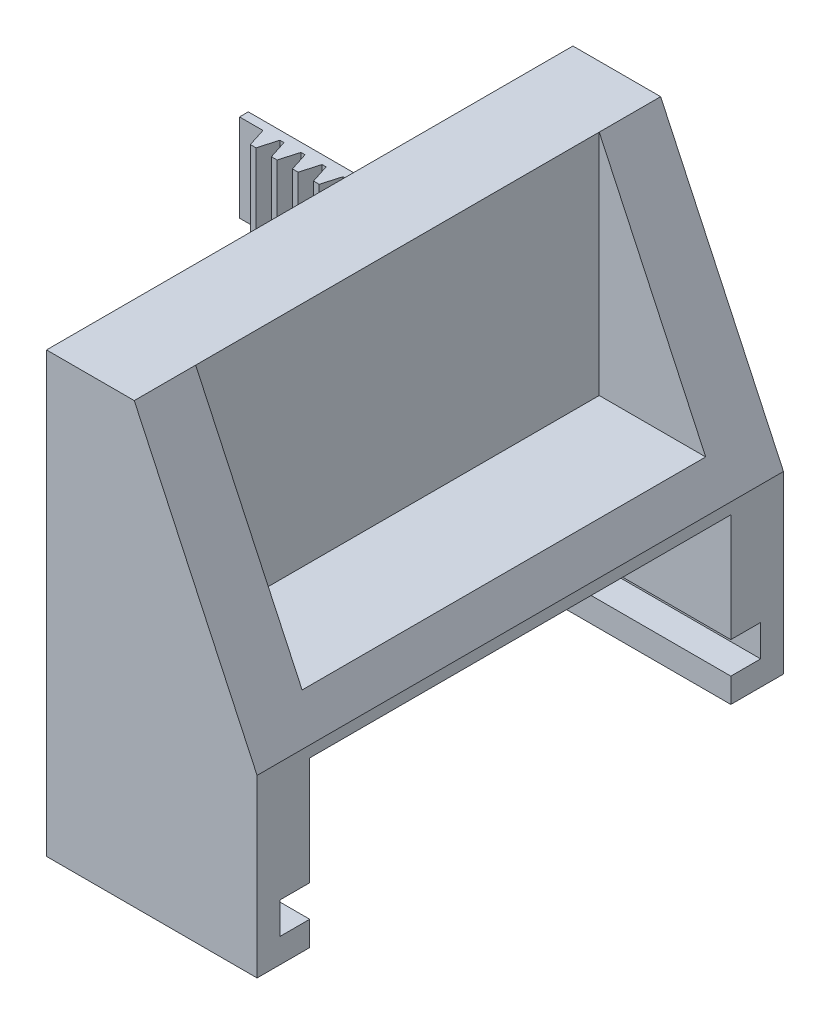
SolidWorks part; units mm, degrees
ref_plane "Front Plane" through (0, 0, 0) normal (0, 0, 1) x (1, 0, 0)
ref_plane "Top Plane" through (0, 0, 0) normal (0, 1, 0) x (1, 0, 0)
ref_plane "Right Plane" through (0, 0, 0) normal (1, 0, 0) x (0, 0, -1)
sketch "Sketch1" plane through (0, 0, 0) normal (0, 0, 1) x (1, 0, 0)
  line L0 (0, 0) -> (0, -25)
  line L1 (0, -25) -> (12, -25)
  line L2 (12, -25) -> (12, -15)
  line L3 (12, -15) -> (5, 0)
  line L4 (5, 0) -> (0, 0)
  dimension "D1" = 25
  dimension "D2" = 12
  dimension "D3" = 10
  dimension "D4" = 5
extrude "Boss-Extrude1" add sketch "Sketch1" against normal blind 30
sketch "Sketch4" plane through (0, 0, 0) normal (-1, 0, 0) x (0, 0, 1)
  line L0 (-30, 0) -> (-30, -25) construction
  line L1 (-27, -15.6386) -> (-3, -15.6386)
  line L2 (-27, -15.6386) -> (-27, -29.6386)
  line L3 (-27, -29.6386) -> (-3, -29.6386)
  line L4 (-3, -15.6386) -> (-3, -29.6386)
  point P4 (-27, -22.6386)
  dimension "D1" = 24
  dimension "D2" = 14
  dimension "D3" = 3
extrude "Cut-Extrude2" cut sketch "Sketch4" against normal blind 25 contours L2 L1 L4 L3
sketch "Sketch5" plane through (0, 0, 0) normal (-1, 0, 0) x (0, 0, 1)
  line L0 (-3, -15.6386) -> (-3, -25) construction
  line L1 (-3, -21.8) -> (-1.3, -21.8)
  line L2 (-3, -21.8) -> (-3, -23.6)
  line L3 (-3, -23.6) -> (-1.3, -23.6)
  line L4 (-1.3, -21.8) -> (-1.3, -23.6)
  line L5 (-3, -25) -> (0, -25) construction
  dimension "D1" = 1.8
  dimension "D2" = 1.7
  dimension "D3" = 1.4
extrude "Cut-Extrude3" cut sketch "Sketch5" against normal blind 15
ref_plane "Plane1" through (0, 0, -15) normal (0, 0, 1) x (1, 0, 0)
mirror "Mirror1" about plane through (0, 0, -15) normal (0, 0, 1) of "Cut-Extrude3"
sketch "Sketch6" plane through (0, 0, -15) normal (0, 0, 1) x (1, 0, 0)
  line L0 (5, 0) -> (5, -13)
  line L1 (5, -13) -> (11.0667, -13)
  line L2 (12, -15) -> (5, 0) construction
  line L3 (11.0667, -13) -> (5, 0)
  dimension "D1" = 13
extrude "Cut-Extrude4" cut sketch "Sketch6" against normal mid plane 23
ref_plane "Plane2" through (0, -15, 0) normal (0, 1, 0) x (1, 0, 0)
sketch "Sketch7" plane through (0, -15, 0) normal (0, 1, 0) x (1, 0, 0)
  line L0 (0, 27.5) -> (-16, 27.5)
  line L1 (0, 30) -> (0, 0) construction
  line L3 (0, 27.5) -> (0, 27)
  line L4 (0, 27) -> (-0.5, 27)
  line L47 (-0.5, 27) -> (-0.8043, 25.9435)
  line L62 (-6.6, 15) -> (6.6, 15) construction
  line L63 (-0.8043, 25.9435) -> (-1.1273, 25.9435)
  line L64 (-1.1273, 25.9435) -> (-1.4655, 27)
  line L65 (-2.3273, 25.9435) -> (-2.6655, 27)
  line L66 (-2.0043, 25.9435) -> (-2.3273, 25.9435)
  line L67 (-1.7, 27) -> (-2.0043, 25.9435)
  line L68 (-3.5273, 25.9435) -> (-3.8655, 27)
  line L69 (-3.2043, 25.9435) -> (-3.5273, 25.9435)
  line L70 (-2.9, 27) -> (-3.2043, 25.9435)
  line L71 (-4.7273, 25.9435) -> (-5.0655, 27)
  line L72 (-4.4043, 25.9435) -> (-4.7273, 25.9435)
  line L73 (-4.1, 27) -> (-4.4043, 25.9435)
  line L74 (-5.9273, 25.9435) -> (-6.2655, 27)
  line L75 (-5.6043, 25.9435) -> (-5.9273, 25.9435)
  line L76 (-5.3, 27) -> (-5.6043, 25.9435)
  line L77 (-7.1273, 25.9435) -> (-7.4655, 27)
  line L78 (-6.8043, 25.9435) -> (-7.1273, 25.9435)
  line L79 (-6.5, 27) -> (-6.8043, 25.9435)
  line L80 (-8.3273, 25.9435) -> (-8.6655, 27)
  line L81 (-8.0043, 25.9435) -> (-8.3273, 25.9435)
  line L82 (-7.7, 27) -> (-8.0043, 25.9435)
  line L83 (-9.5273, 25.9435) -> (-9.8655, 27)
  line L84 (-9.2043, 25.9435) -> (-9.5273, 25.9435)
  line L85 (-8.9, 27) -> (-9.2043, 25.9435)
  line L86 (-10.7273, 25.9435) -> (-11.0655, 27)
  line L87 (-10.4043, 25.9435) -> (-10.7273, 25.9435)
  line L88 (-10.1, 27) -> (-10.4043, 25.9435)
  line L89 (-11.9273, 25.9435) -> (-12.2655, 27)
  line L90 (-11.6043, 25.9435) -> (-11.9273, 25.9435)
  line L91 (-11.3, 27) -> (-11.6043, 25.9435)
  line L92 (-13.1273, 25.9435) -> (-13.4655, 27)
  line L93 (-12.8043, 25.9435) -> (-13.1273, 25.9435)
  line L94 (-12.5, 27) -> (-12.8043, 25.9435)
  line L95 (-14.3273, 25.9435) -> (-14.6655, 27)
  line L96 (-14.0043, 25.9435) -> (-14.3273, 25.9435)
  line L97 (-13.7, 27) -> (-14.0043, 25.9435)
  line L98 (-1.4655, 27) -> (-1.7, 27)
  line L99 (-2.6655, 27) -> (-2.9, 27)
  line L100 (-3.8655, 27) -> (-4.1, 27)
  line L101 (-5.0655, 27) -> (-5.3, 27)
  line L102 (-6.2655, 27) -> (-6.5, 27)
  line L103 (-7.4655, 27) -> (-7.7, 27)
  line L104 (-8.6655, 27) -> (-8.9, 27)
  line L105 (-9.8655, 27) -> (-10.1, 27)
  line L106 (-11.0655, 27) -> (-11.3, 27)
  line L107 (-14.9, 27) -> (-16, 27)
  line L108 (-16, 27) -> (-16, 27.5)
  line L109 (-12.2655, 27) -> (-12.5, 27)
  line L110 (-13.4655, 27) -> (-13.7, 27)
  line L111 (-14.6655, 27) -> (-14.9, 27)
  dimension "D1" = 12
  dimension "D2" = 16
  dimension "D3" = 0.5
  dimension "D6" = 0.5
  dimension "D7" = 12.5
extrude "Boss-Extrude2" add sketch "Sketch7" along normal blind 5
